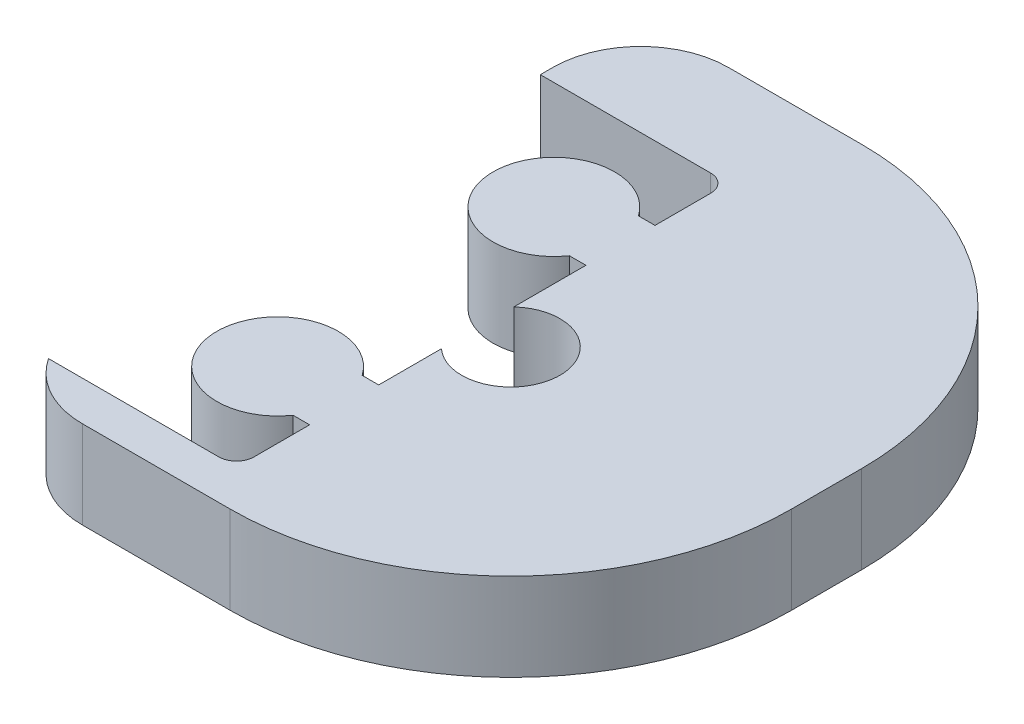
SolidWorks part; units mm, degrees
ref_plane "Front Plane" through (0, 0, 0) normal (0, 0, 1) x (1, 0, 0)
ref_plane "Top Plane" through (0, 0, 0) normal (0, 1, 0) x (1, 0, 0)
ref_plane "Right Plane" through (0, 0, 0) normal (1, 0, 0) x (0, 0, -1)
sketch "Sketch1" plane through (0, 0, 0) normal (0, 1, 0) x (1, 0, 0)
  line L1 (-25.4, 11.43) -> (25.4, 11.43)
  line L2 (-25.4, 11.43) -> (-25.4, -11.43)
  line L3 (-25.4, -11.43) -> (25.4, -11.43)
  line L4 (25.4, 11.43) -> (25.4, -11.43)
  dimension "D1" = 22.86
  dimension "D2" = 50.8
  dimension "D3" = 11.43
  dimension "D4" = 25.4
extrude "Boss-Extrude1" add sketch "Sketch1" along normal blind 3.175
fillet "Fillet1" radius 10.16 2 edges at (-25.4, 1.5875, 11.43) (25.4, 1.5875, 11.43)
sketch "Sketch3" plane through (0, 3.175, 0) normal (0, 1, 0) x (1, 0, 0)
  line L0 (-7.7526, -1.27) -> (18.5521, -1.27) construction
  circle A0 centre (15.24, -1.27) radius 1.778
  arc A2 (15.24, -11.43) -> (25.4, -1.27) centre (15.24, -1.27) ccw construction
  circle A3 centre (-3.81, -1.27) radius 1.778
  dimension "D1" = 3.556
  dimension "D6" = 3.556
  dimension "D5" = 19.05
extrude "Cut-Extrude1" cut sketch "Sketch3" against normal through all
fillet "Fillet3" radius 10.16 2 edges at (-25.4, 1.5875, -11.43) (25.4, 1.5875, -11.43)
sketch "Sketch5" plane through (0, 0, 0) normal (0, -1, 0) x (1, 0, 0)
  line L0 (7.239, -11.43) -> (7.239, -7.7991)
  line L1 (25.4, 1.27) -> (25.4, -1.27) construction
  line L2 (14.039, -2.6491) -> (14.039, 4.8509)
  line L3 (13.439, -2.6491) -> (14.039, -2.6491)
  line L4 (13.439, -5.1491) -> (14.039, -5.1491)
  line L5 (15.24, -11.43) -> (-15.24, -11.43) construction
  line L6 (7.239, 11.43) -> (-25.4, 11.43)
  line L7 (-15.24, 11.43) -> (15.24, 11.43) construction
  line L8 (7.239, -11.43) -> (-25.4, -11.43)
  line L9 (-25.4, 11.43) -> (-25.4, -11.43)
  line L10 (-25.4, -1.27) -> (-25.4, 1.27) construction
  line L11 (13.439, 4.8509) -> (14.039, 4.8509)
  line L12 (13.439, 7.3509) -> (14.039, 7.3509)
  line L13 (-15.24, 11.43) -> (15.24, 11.43) construction
  line L14 (7.239, 11.43) -> (7.239, 10.0009)
  line L15 (13.039, -7.7991) -> (7.039, -7.7991) construction
  line L16 (13.039, 10.0009) -> (7.039, 10.0009) construction
  line L17 (7.239, -7.7991) -> (14.039, -7.7991)
  line L18 (14.039, -7.7991) -> (14.039, -5.1491)
  line L19 (14.039, 7.3509) -> (14.039, 10.0009)
  line L20 (14.039, 10.0009) -> (7.239, 10.0009)
  arc A0 (13.439, -5.1491) -> (13.439, -2.6491) centre (11.6286, -3.8991) cw
  arc A1 (13.439, 4.8509) -> (13.439, 7.3509) centre (11.6286, 6.1009) cw
  dimension "D1" = 2.2
  dimension "D2" = 2.2
  dimension "D3" = 18.161
extrude "Cut-Extrude3" cut sketch "Sketch5" against normal through all contours L8 L9 L6 L14 L20 L19 L12 A1 L11 L2 L3 A0 L4 L18 L17 L0
fillet "Fillet4" radius 0.635 2 edges at (14.039, 1.5875, 10.0009) (14.039, 1.5875, -7.7991)
fillet "Fillet5" radius 3.175 2 edges at (7.239, 1.5875, 11.43) (7.239, 1.5875, -11.43)
equation "\"D4@Sketch1\"=\"D2@Sketch1\"/2"
equation "\"D3@Sketch1\"=\"D1@Sketch1\"/2"
